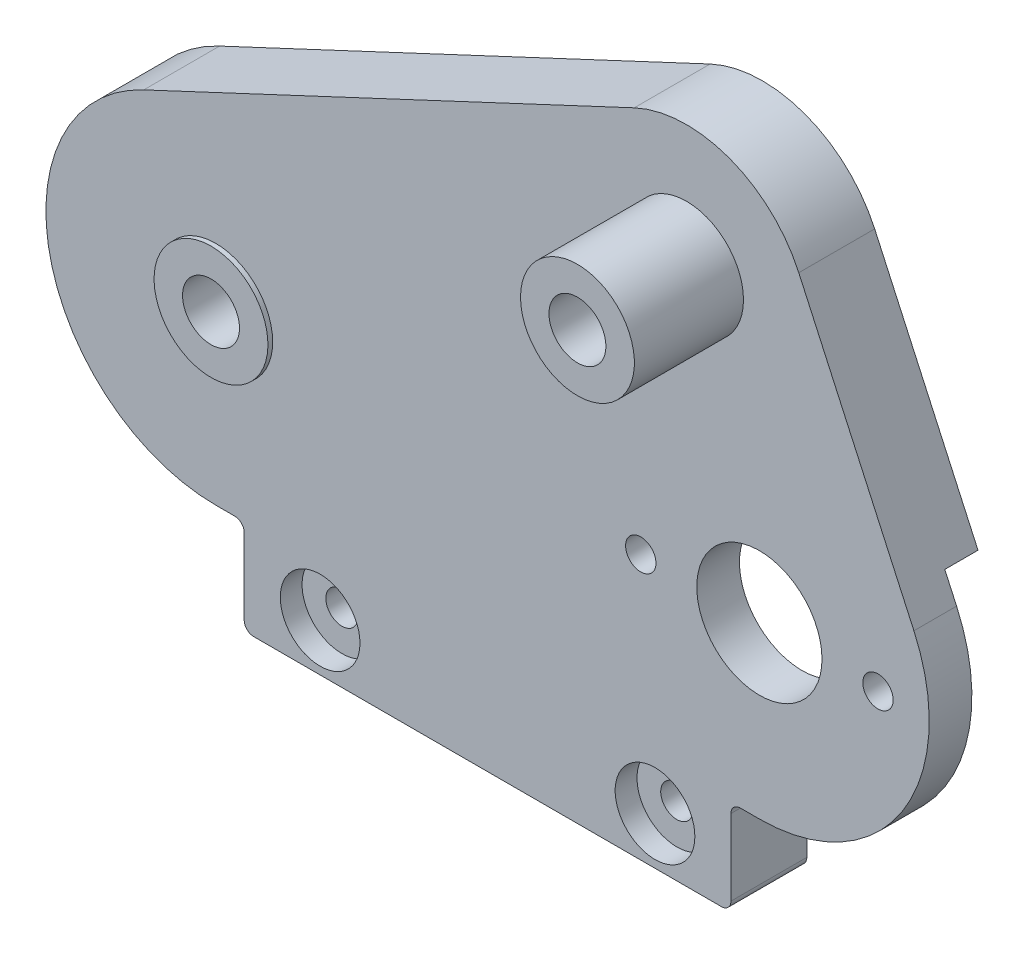
SolidWorks part; units mm, degrees
ref_plane "Front Plane" through (0, 0, 0) normal (0, 0, 1) x (1, 0, 0)
ref_plane "Top Plane" through (0, 0, 0) normal (0, 1, 0) x (1, 0, 0)
ref_plane "Right Plane" through (0, 0, 0) normal (1, 0, 0) x (0, 0, -1)
sketch "Sketch1" plane through (0, 0, 0) normal (0, 0, 1) x (1, 0, 0)
  circle A0 centre (0, 0) radius 6.6
  circle A1 centre (0, 0) radius 17.9
  dimension "D1" = 13.2
  dimension "D2" = 35.8
extrude "Boss-Extrude1" add sketch "Sketch1" along normal blind 4.5
sketch "Sketch2" plane through (0, 0, 4.5) normal (0, 0, 1) x (1, 0, 0)
  line L0 (12.5, 0) -> (-12.5, 0) construction
  point P0 (-12.5, 0)
  point P6 (0, 0)
  point P8 (12.5, 0)
  dimension "D1" = 25
hole_wizard "Ø3.2 (3.2) Diameter Hole1" positions "Sketch5" profile "Sketch6" hole size "Ø3.2" standard "ANSI Metric"
sketch "Sketch5" plane through (0, 0, 4.5) normal (0, 0, 1) x (1, 0, 0)
  point P0 (-12.5, 0)
  point P3 (12.5, 0)
sketch "Sketch6" plane through (-12.5, 0, 4.5) normal (1, 0, 0) x (0, -1, 0)
  line L0 (0, 0) -> (0, 5.4614)
  line L1 (0, 5.4614) -> (1.6, 4.5)
  line L2 (1.6, 4.5) -> (1.6, 0)
  line L5 (1.6, 0) -> (0, 0)
  line L10 (0, 5.4614) -> (-1.6, 4.5) construction
  line L11 (0, -6.35) -> (0, 107.95) construction
  dimension "Hole Dia." = 3.2
  dimension "Hole Depth" = 4.5
  dimension "Drill Angle" = 118
sketch "Sketch7" plane through (0, 0, 4.5) normal (0, 0, 1) x (1, 0, 0)
  line L0 (0, -17.9) -> (-57.2987, -17.9)
  line L1 (-57.2987, 17.9) -> (0, 17.9)
  line L2 (-57.2987, 0) -> (0, 0) construction
  circle A0 centre (0, 0) radius 17.9 construction
  arc A1 (-57.2987, -17.9) -> (-57.2987, 17.9) centre (-57.2987, 0) cw
  arc A2 (0, 17.9) -> (0, -17.9) centre (0, 0) ccw
extrude "Boss-Extrude3" add sketch "Sketch7" against normal blind 8
sketch "Sketch8" plane through (0, 0, 4.5) normal (0, 0, 1) x (1, 0, 0)
  circle A0 centre (-57.2987, 0) radius 3
  dimension "D1" = 6
extrude "Cut-Extrude1" cut sketch "Sketch8" against normal through all both and the other way through all contours A0
sketch "Sketch10" plane through (0, 0, 0) normal (0, 0, -1) x (-1, 0, 0)
  line L0 (13.19, 40.4223) -> (64.8902, 16.2104)
  line L1 (-4.1521, 34.0422) -> (-16.2871, 7.4256)
  line L2 (57.2987, 17.9) -> (0, 17.9) construction
  line L3 (57.2987, 17.9) -> (0, 17.9)
  arc A0 (13.19, 40.4223) -> (-4.1521, 34.0422) centre (7.6766, 28.6493) ccw
  arc A1 (0, 17.9) -> (0, -17.9) centre (0, 0) ccw construction
  arc A2 (57.2987, -17.9) -> (57.2987, 17.9) centre (57.2987, 0) ccw construction
  circle A3 centre (7.6766, 28.6493) radius 3 construction
  arc A4 (0, 17.9) -> (-16.2871, 7.4256) centre (0, 0) ccw
  arc A5 (64.8902, 16.2104) -> (57.2987, 17.9) centre (57.2987, 0) ccw
  circle A7 centre (7.6766, 28.6493) radius 3
  dimension "D1" = 10
extrude "Boss-Extrude4" add sketch "Sketch10" against normal up to surface and the other way up to surface up to face at (-54.2987, 0, 4.5) other way up to face at (-54.2987, 0, -3.5)
sketch "Sketch14" plane through (0, 0, 4.5) normal (0, 0, 1) x (1, 0, 0)
  circle A0 centre (-57.2987, 0) radius 6
  circle A1 centre (-57.2987, 0) radius 3 construction
  circle A2 centre (-57.2987, 0) radius 3
  dimension "D1" = 3
extrude "Boss-Extrude5" add sketch "Sketch14" along normal up to surface (0.5 mm away)
sketch "Sketch15" plane through (0, 0, 4.5) normal (0, 0, 1) x (1, 0, 0)
  circle A0 centre (-7.6766, 28.6493) radius 3 construction
  circle A1 centre (-7.6766, 28.6493) radius 3
  circle A2 centre (-7.6766, 28.6493) radius 6
  dimension "D1" = 3
extrude "Boss-Extrude6" add sketch "Sketch15" along normal up to surface (11.5 mm away)
sketch "Sketch16" plane through (0, 0, 4.5) normal (0, 0, 1) x (1, 0, 0)
  line L0 (-54.2987, -27.9) -> (-3, -27.9)
  line L1 (-3, -27.9) -> (-3, -17.9)
  line L2 (-57.2987, -17.9) -> (0, -17.9) construction
  line L3 (-3, -17.9) -> (-54.2987, -17.9)
  line L4 (-54.2987, -17.9) -> (-54.2987, -27.9)
  dimension "D1" = 3
  dimension "D2" = 3
  dimension "D3" = 10
extrude "Boss-Extrude7" add sketch "Sketch16" against normal up to surface (8 mm away) up to face at (-25.0807, 12.9656, -3.5)
hole_wizard "CBORE for M3 Hex Head Machine Screw1" positions "Sketch17" profile "Sketch18" counterbore size "M3" standard "ANSI Metric" end condition through all
sketch "Sketch17" plane through (0, 0, 4.5) normal (0, 0, 1) x (1, 0, 0)
  line L0 (-54.2987, -22.9) -> (-3, -22.9) construction
  line L1 (-54.2987, -17.9) -> (-54.2987, -27.9) construction
  line L2 (-3, -27.9) -> (-3, -17.9) construction
  point P9 (-46.2987, -22.9)
  point P11 (-11, -22.9)
  dimension "D1" = 8
  dimension "D2" = 8
sketch "Sketch18" plane through (-11, -22.9, 4.5) normal (1, 0, 0) x (0, -1, 0)
  line L0 (0, 0) -> (0, 8)
  line L1 (0, 8) -> (1.7, 8)
  line L3 (1.7, 8) -> (1.7, 2.3)
  line L4 (1.7, 2.3) -> (4.2, 2.3)
  line L5 (4.2, 2.3) -> (4.2, 0)
  line L7 (4.2, 0) -> (0, 0)
  line L11 (0, -6.35) -> (0, 107.95) construction
  dimension "Thru Hole Dia." = 3.4
  dimension "Thru Hole Depth" = 8
  dimension "C'Bore Dia." = 8.4
  dimension "C'Bore Depth" = 2.3
sketch "Sketch20" plane through (0, 0, -3.5) normal (0, 0, -1) x (-1, 0, 0)
  line L0 (3, -17.9) -> (0, -17.9) construction
  line L1 (3, -17.9) -> (0, -17.9)
  line L2 (3, -17.9) -> (3, -17.6468)
  line L3 (-16.2871, 7.4256) -> (-4.1521, 34.0422) construction
  line L4 (-16.2871, 7.4256) -> (-15.0426, 10.1553)
  line L5 (-15.0426, 10.1553) -> (-14.8122, 10.0503)
  arc A0 (0, -17.9) -> (-16.2871, 7.4256) centre (0, 0) ccw construction
  arc A1 (0, -17.9) -> (3, -17.6468) centre (0, 0) ccw
  arc A2 (0, -17.9) -> (-16.2871, 7.4256) centre (0, 0) ccw
  arc A3 (-16.2871, 7.4256) -> (0, -17.9) centre (0, 0) ccw
  arc A4 (0, -17.9) -> (3, -17.6468) centre (0, 0) ccw
  arc A6 (-14.8122, 10.0503) -> (-16.2871, 7.4256) centre (0, 0) ccw
  line M10 (-4.1521, 34.0422) -> (-16.2871, 7.4256)
  arc M11 (-16.2871, 7.4256) -> (0, -17.9) centre (0, 0) cw
  line M12 (0, -17.9) -> (3, -17.9)
  dimension "D2" = 3
  dimension "D1" = 0
extrude "Cut-Extrude2" cut sketch "Sketch20" against normal up to surface (3.5 mm away) contours L5 M10 M11 | L2 M12 M11 region at (-2.2511, -17.8241, -3.5) region at (15.2843, 9.4424, -3.5) up to face at (0, 0, 0)
fillet "Fillet1" radius 1 4 edges at (-3, -27.9, 0.5) (-3, -17.9, 2.25) (-54.2987, -27.9, 0.5) (-54.2987, -17.9, 0.5)
